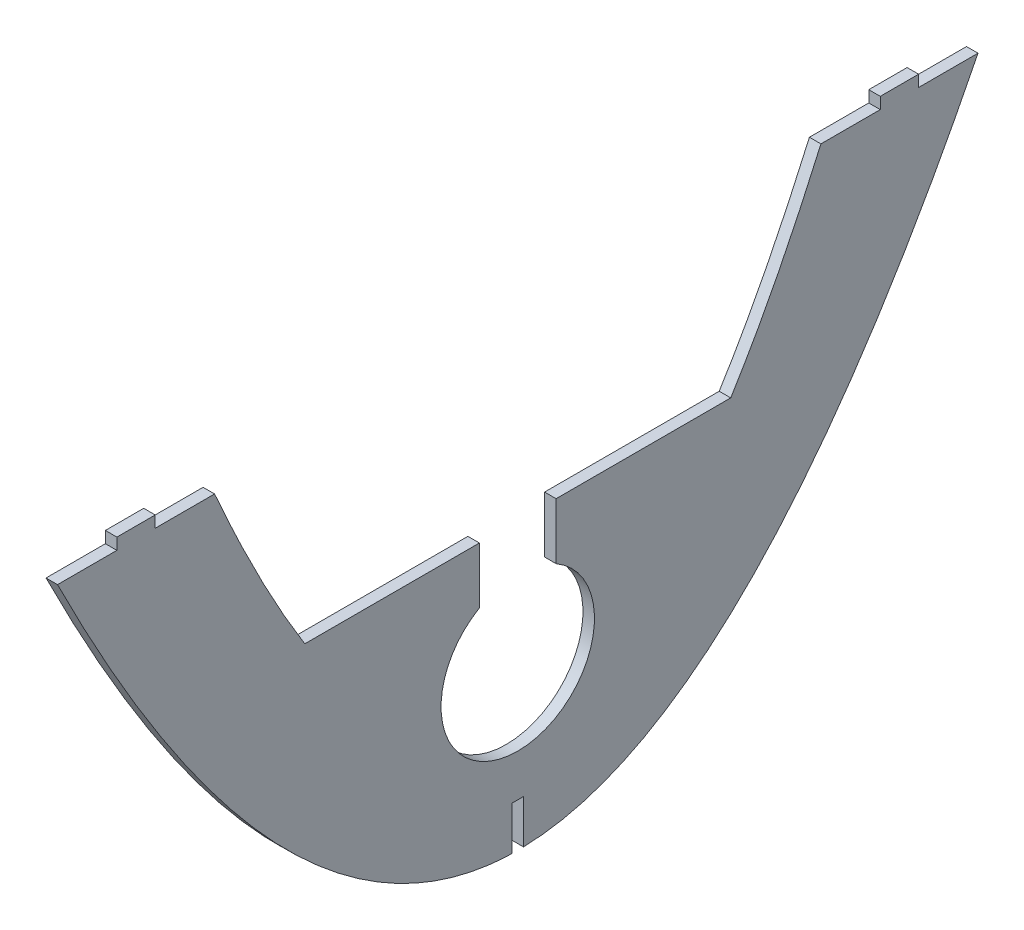
SolidWorks part; units mm, degrees
ref_plane "前视基准面" through (0, 0, 0) normal (0, 0, 1) x (1, 0, 0)
ref_plane "上视基准面" through (0, 0, 0) normal (0, 1, 0) x (1, 0, 0)
ref_plane "右视基准面" through (0, 0, 0) normal (1, 0, 0) x (0, 0, -1)
sketch "草图1" plane through (0, 0, 0) normal (1, 0, 0) x (0, 0, -1)
  line L0 (-120, 119.9952) -> (-79.0439, 119.9952)
  line L1 (79.0439, 119.9952) -> (120, 119.9952)
  spline S0 degree 2 poles (-135.144, 152.193) (0, -152.193) (135.144, 152.193) knots 0 0 0 1 1 1 construction
  spline S1 degree 2 poles (-120, 119.9952) (0, -119.9952) (120, 119.9952) knots 0.056029 0.056029 0.056029 0.943971 0.943971 0.943971
  spline S2 degree 2 poles (-133.2388, 285.7081) (0, -225.7081) (133.2388, 285.7081) knots 0 0 0 1 1 1 construction
  spline S3 degree 2 poles (-79.0439, 119.9952) (0, -59.9952) (79.0439, 119.9952) knots 0.203375 0.203375 0.203375 0.796625 0.796625 0.796625
extrude "凸台-拉伸1" add sketch "草图1" along normal blind 3
sketch "草图2" plane through (0, 119.9952, 0) normal (0, 1, 0) x (1, 0, 0)
  line L0 (0, -120) -> (3, -79.0439)
  line L1 (0, 120) -> (3, 79.0439)
  line L2 (3, 120) -> (3, 79.0439) construction
  line L3 (0, 94.5219) -> (3, 94.5219)
  line L4 (0, 94.5219) -> (0, 104.5219)
  line L5 (0, 104.5219) -> (3, 104.5219)
  line L6 (3, 94.5219) -> (3, 104.5219)
  line L7 (0, 94.5219) -> (3, 104.5219) construction
  line L8 (0, 104.5219) -> (3, 94.5219) construction
  line L9 (0, -79.0439) -> (0, -120) construction
  line L10 (3, -104.5219) -> (0, -104.5219)
  line L11 (3, -104.5219) -> (3, -94.5219)
  line L12 (3, -94.5219) -> (0, -94.5219)
  line L13 (0, -104.5219) -> (0, -94.5219)
  line L14 (3, -104.5219) -> (0, -94.5219) construction
  line L15 (3, -94.5219) -> (0, -104.5219) construction
  point P8 (1.5, 99.5219)
  point P15 (1.5, -99.5219)
  line M3 (0, -79.0439) -> (0, -120)
  line M5 (3, -120) -> (3, -79.0439)
extrude "凸台-拉伸2" add sketch "草图2" along normal blind 3 contours L0 L12 L10 M3 | L12 L0 L10 M5 | L4 L5 L6 L3 region at (0.7649, 119.9952, 99.115) region at (2.2351, 119.9952, 99.9289)
sketch "草图3" plane through (3, 0, 0) normal (1, 0, 0) x (0, 0, -1)
  line L0 (0, 0) -> (0, 22.4)
  line L1 (0, 0) -> (0, 22.4)
  line L3 (-55.5201, 74.4) -> (-10, 74.4)
  line L4 (10, 74.4) -> (55.5201, 74.4)
  line L6 (-10, 59.7205) -> (-10, 74.4)
  line L8 (10, 59.7205) -> (10, 74.4)
  line L11 (0, 42.1404) -> (0, 42.4)
  arc A0 (-10, 59.7205) -> (10, 59.7205) centre (0, 42.4) ccw
  parabola Q0 (79.0439, 119.9952) -> (-79.0439, 119.9952) focus (0, 47.3563) apex (0, 30) construction
  parabola Q1 (79.0439, 119.9952) -> (-79.0439, 119.9952) focus (0, 47.3563) apex (0, 30) construction
  parabola Q2 (79.0439, 119.9952) -> (-79.0439, 119.9952) focus (0, 47.3563) apex (0, 30) construction
  parabola Q3 (55.5201, 74.4) -> (18.5668, 34.9655) focus (0, 47.3563) apex (0, 30)
  parabola Q4 (-18.5668, 34.9655) -> (-55.5201, 74.4) focus (0, 47.3563) apex (0, 30)
  point P22 (0, 62.4)
  spline M2 degree 2 poles (79.0439, 119.9952) (0, -59.9952) (-79.0439, 119.9952) knots 0.203375 0.203375 0.203375 0.796625 0.796625 0.796625
extrude "凸台-拉伸3" add sketch "草图3" against normal blind 3 contours A0 L6 L3 M2 | A0 L4 L8 M2 region at (3, 61.0746, -29.2152) region at (3, 61.0746, 29.2152)
extrude "切除-拉伸1" cut sketch "草图3<3>" against normal blind 3 and the other way through all contours A0 M2 region at (3, 27.9404, 0)
sketch "草图3<3>" plane through (3, 0, 0) normal (1, 0, 0) x (0, 0, -1) same geometry as "草图3"
sketch "草图4" plane through (0, 0, 0) normal (-1, 0, 0) x (0, 0, 1)
  line L1 (-1.5, 11.4) -> (1.5, 11.4)
  line L2 (-1.5, 11.4) -> (-1.5, -3.9306)
  line L3 (-1.5, -3.9306) -> (1.5, -3.9306)
  line L4 (1.5, 11.4) -> (1.5, -3.9306)
extrude "切除-拉伸2" cut sketch "草图4" against normal through all
